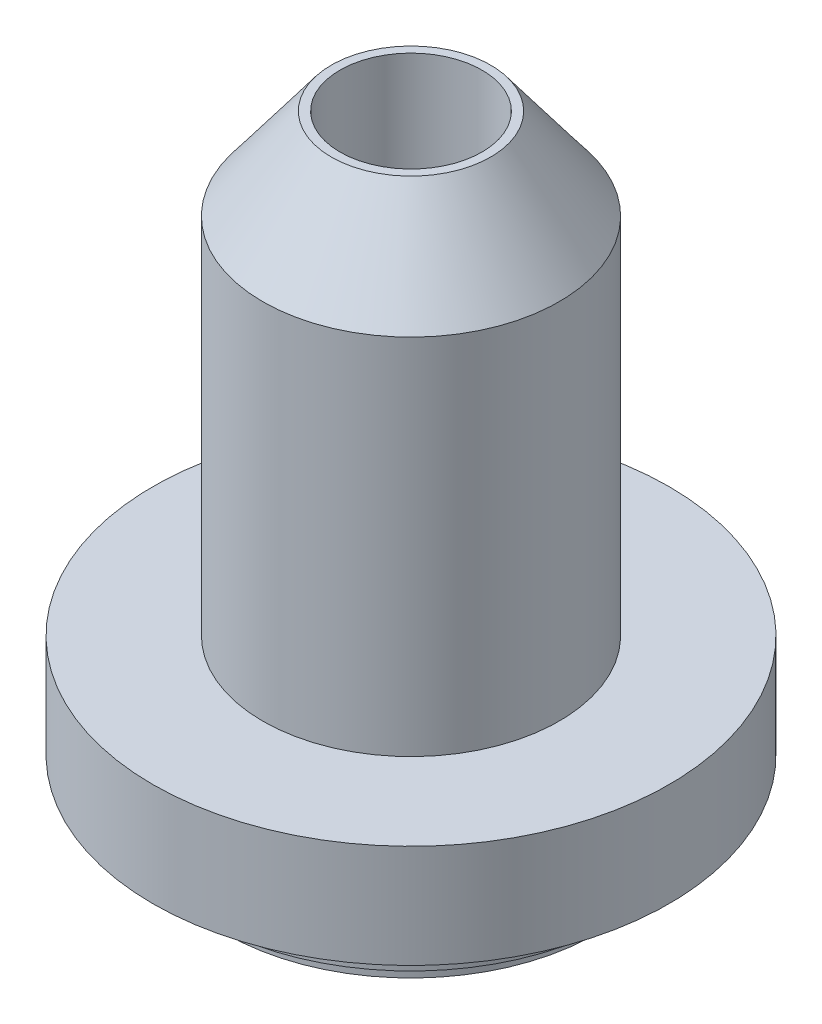
SolidWorks part; units mm, degrees
material "AISI 304"
ref_plane "Front Plane" through (0, 0, 0) normal (0, 0, 1) x (1, 0, 0)
ref_plane "Top Plane" through (0, 0, 0) normal (0, 1, 0) x (1, 0, 0)
ref_plane "Right Plane" through (0, 0, 0) normal (1, 0, 0) x (0, 0, -1)
sketch "Sketch1" plane through (0, 0, 0) normal (0, 1, 0) x (1, 0, 0)
  circle A0 centre (0, 0) radius 7.9375
  dimension "D1" = 15.875
extrude "Boss-Extrude1" add sketch "Sketch1" along normal blind 3.175
sketch "Sketch2" plane through (0, 0, 0) normal (0, -1, 0) x (1, 0, 0)
  circle A1 centre (0, 0) radius 6.35
  dimension "D1" = 12.7
extrude "Boss-Extrude2" add sketch "Sketch2" along normal blind 1.27
sketch "Sketch3" plane through (0, -1.27, 0) normal (0, -1, 0) x (1, 0, 0)
  circle A0 centre (0, 0) radius 5.715
  circle A1 centre (0, 0) radius 6.35 construction
  dimension "D1" = 0.635
extrude "Boss-Extrude3" add sketch "Sketch3" along normal blind 0.635
sketch "Sketch4" plane through (0, 3.175, 0) normal (0, 1, 0) x (1, 0, 0)
  circle A0 centre (0, 0) radius 4.5593
  dimension "D1" = 9.1186
extrude "Boss-Extrude4" add sketch "Sketch4" along normal blind 13.97
sketch "Sketch5" plane through (0, 17.145, 0) normal (0, 1, 0) x (1, 0, 0)
  circle A0 centre (0, 0) radius 2.4511
  circle A1 centre (0, 0) radius 10.1634
  dimension "D1" = 4.9022
extrude "Cut-Extrude1" cut sketch "Sketch5" against normal through all draft 37
sketch "Sketch6" plane through (0, 17.145, 0) normal (0, 1, 0) x (1, 0, 0)
  circle A0 centre (0, 0) radius 2.1844
  dimension "D1" = 4.3688
extrude "Cut-Extrude2" cut sketch "Sketch6" against normal through all
